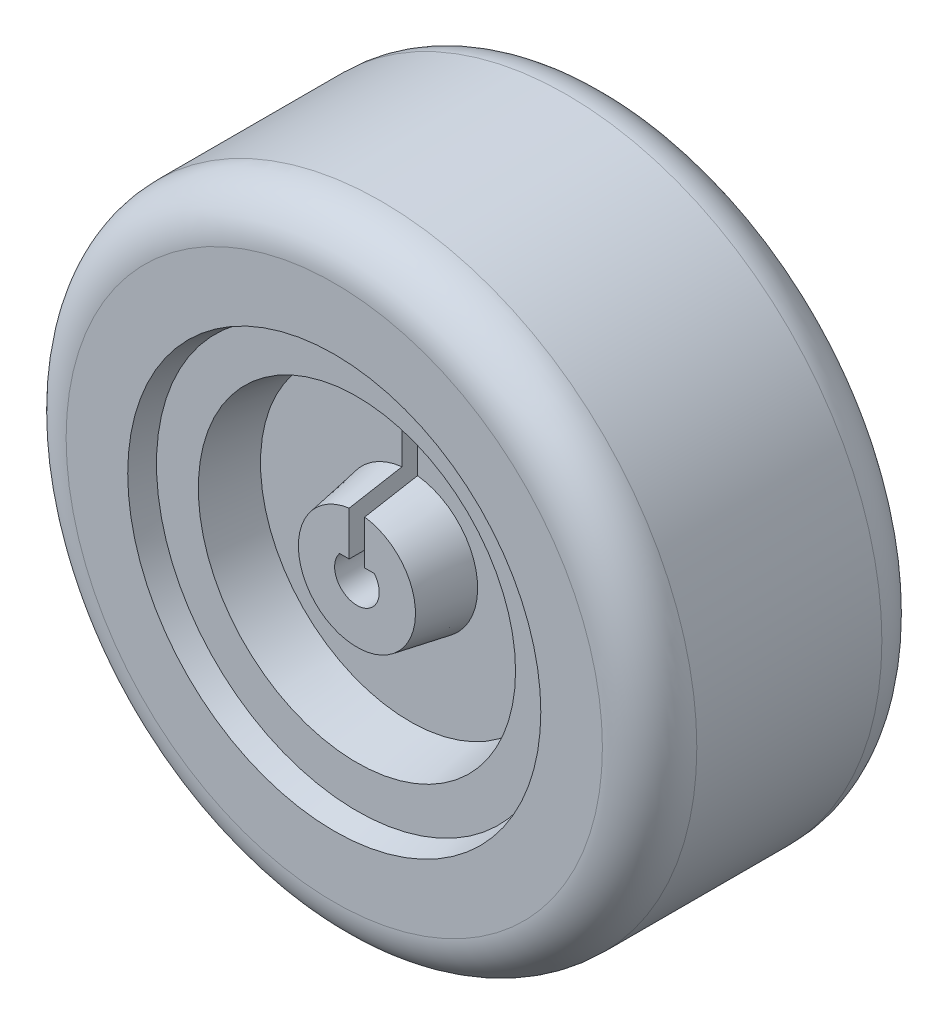
SolidWorks part; units mm, degrees
ref_plane "Front Plane" through (0, 0, 0) normal (0, 0, 1) x (1, 0, 0)
ref_plane "Top Plane" through (0, 0, 0) normal (0, 1, 0) x (1, 0, 0)
ref_plane "Right Plane" through (0, 0, 0) normal (1, 0, 0) x (0, 0, -1)
sketch "Sketch1" plane through (0, 0, 0) normal (0, 0, 1) x (1, 0, 0)
  circle A0 centre (0, 0) radius 21.209
  circle A1 centre (0, 0) radius 13.208
  dimension "D1" = 42.418
  dimension "D2" = 26.416
extrude "Boss-Extrude1" add sketch "Sketch1" along normal blind 18.796
fillet "Fillet1" radius 3.175 2 edges at (21.209, 0, 0) (21.209, 0, 18.796)
sketch "Sketch2" plane through (0, 0, 18.796) normal (0, 0, 1) x (1, 0, 0)
  circle A0 centre (0, 0) radius 13.208
  circle A1 centre (0, 0) radius 13.208 construction
extrude "Boss-Extrude2" add sketch "Sketch2" against normal offset from surface (15.748 mm away) 1.524 from offset 1.524 separate body up to face at (18.034, 0, 0) offset against normal yes
sketch "Sketch4" plane through (0, 0, 17.272) normal (0, 0, 1) x (1, 0, 0)
  circle A0 centre (0, 0) radius 3.937
  circle A2 centre (0, 0) radius 10.668
  circle A3 centre (0, 0) radius 10.668
  dimension "D2" = 7.874
  dimension "D1" = 2.54
extrude "Cut-Extrude2" cut sketch "Sketch4" against normal blind 3.556 draft 10
sketch "Sketch5" plane through (0, 0, 1.524) normal (0, 0, -1) x (-1, 0, 0)
  circle A3 centre (0, 0) radius 10.668
  circle A4 centre (0, 0) radius 10.668
  dimension "D1" = 2.54
extrude "Cut-Extrude3" cut sketch "Sketch5" against normal offset from surface (9.652 mm away) 2.54 up to face at (4.564, 0, 13.716)
sketch "Sketch6" plane through (0, 0, 11.176) normal (0, 0, -1) x (-1, 0, 0)
  circle A0 centre (0, 0) radius 4.1275
  circle A3 centre (0, 0) radius 10.668 construction
  dimension "D1" = 8.255
extrude "Boss-Extrude3" add sketch "Sketch6" along normal blind 3.81 draft 10
sketch "Sketch3" plane through (0, 0, 17.272) normal (0, 0, 1) x (1, 0, 0)
  line L0 (-1.1702, 0.9384) -> (-0.5207, 0.9384)
  line L1 (0, -1.5) -> (0, 0.9384) construction
  line L2 (0.5207, 0.9384) -> (1.1702, 0.9384)
  line L4 (-0.5207, 0.9384) -> (-0.5207, 6.7108)
  line L5 (-0.5207, 6.7108) -> (0.5207, 6.7108)
  line L6 (0.5207, 0.9384) -> (0.5207, 6.7108)
  line L7 (-0.5207, -4.834) -> (0.5207, 6.7108) construction
  line L8 (-0.5207, 6.7108) -> (0.5207, -4.834) construction
  arc A0 (-1.1702, 0.9384) -> (1.1702, 0.9384) centre (0, 0) ccw
  dimension "D1" = 3
  dimension "D2" = 2.4384
  dimension "D3" = 1.0414
extrude "Cut-Extrude1" cut sketch "Sketch3" against normal blind 20.32
chamfer "Chamfer2" distance 2.54 angle 15.06 1 edges at (13.208, 0, 18.796) first distance on face at (13.208, 0, 17.272)
chamfer "Chamfer3" distance 2.54 angle 15.06 1 edges at (13.208, 0, 0) first distance on face at (13.208, 0, 0)
sketch "Sketch8" plane through (0, 0, 1.524) normal (0, 0, -1) x (-1, 0, 0)
  line L0 (0, 0) -> (6.7819, 25.3104) construction
  line L1 (1.9316, 13.3423) -> (0.2675, 7.1318)
  line L2 (4.9984, 12.5205) -> (3.3343, 6.31)
  line L3 (0.2675, 7.1318) -> (3.3343, 6.31)
  line L4 (0, 0) -> (0, 28.6093) construction
  line L5 (8.3439, 10.589) -> (3.7975, 6.0426)
  line L6 (10.589, 8.3439) -> (6.0426, 3.7975)
  line L7 (3.7975, 6.0426) -> (6.0426, 3.7975)
  line L8 (12.5205, 4.9984) -> (6.31, 3.3343)
  line L9 (13.3423, 1.9316) -> (7.1318, 0.2675)
  line L10 (6.31, 3.3343) -> (7.1318, 0.2675)
  line L11 (13.3423, -1.9316) -> (7.1318, -0.2675)
  line L12 (12.5205, -4.9984) -> (6.31, -3.3343)
  line L13 (7.1318, -0.2675) -> (6.31, -3.3343)
  line L14 (10.589, -8.3439) -> (6.0426, -3.7975)
  line L15 (8.3439, -10.589) -> (3.7975, -6.0426)
  line L16 (6.0426, -3.7975) -> (3.7975, -6.0426)
  line L17 (4.9984, -12.5205) -> (3.3343, -6.31)
  line L18 (1.9316, -13.3423) -> (0.2675, -7.1318)
  line L19 (3.3343, -6.31) -> (0.2675, -7.1318)
  line L20 (-1.9316, -13.3423) -> (-0.2675, -7.1318)
  line L21 (-4.9984, -12.5205) -> (-3.3343, -6.31)
  line L22 (-0.2675, -7.1318) -> (-3.3343, -6.31)
  line L23 (-8.3439, -10.589) -> (-3.7975, -6.0426)
  line L24 (-10.589, -8.3439) -> (-6.0426, -3.7975)
  line L25 (-3.7975, -6.0426) -> (-6.0426, -3.7975)
  line L26 (-12.5205, -4.9984) -> (-6.31, -3.3343)
  line L27 (-13.3423, -1.9316) -> (-7.1318, -0.2675)
  line L28 (-6.31, -3.3343) -> (-7.1318, -0.2675)
  line L29 (-13.3423, 1.9316) -> (-7.1318, 0.2675)
  line L30 (-12.5205, 4.9984) -> (-6.31, 3.3343)
  line L31 (-7.1318, 0.2675) -> (-6.31, 3.3343)
  line L32 (-10.589, 8.3439) -> (-6.0426, 3.7975)
  line L33 (-8.3439, 10.589) -> (-3.7975, 6.0426)
  line L34 (-6.0426, 3.7975) -> (-3.7975, 6.0426)
  line L35 (-4.9984, 12.5205) -> (-3.3343, 6.31)
  line L36 (-1.9316, 13.3423) -> (-0.2675, 7.1318)
  line L37 (-3.3343, 6.31) -> (-0.2675, 7.1318)
  circle A0 centre (0, 0) radius 13.4814 construction
  arc A1 (4.9984, 12.5205) -> (1.9316, 13.3423) centre (0, 0) ccw
  arc A2 (10.589, 8.3439) -> (8.3439, 10.589) centre (0, 0) ccw
  arc A3 (13.3423, 1.9316) -> (12.5205, 4.9984) centre (0, 0) ccw
  arc A4 (12.5205, -4.9984) -> (13.3423, -1.9316) centre (0, 0) ccw
  arc A5 (8.3439, -10.589) -> (10.589, -8.3439) centre (0, 0) ccw
  arc A6 (1.9316, -13.3423) -> (4.9984, -12.5205) centre (0, 0) ccw
  arc A7 (-4.9984, -12.5205) -> (-1.9316, -13.3423) centre (0, 0) ccw
  arc A8 (-10.589, -8.3439) -> (-8.3439, -10.589) centre (0, 0) ccw
  arc A9 (-13.3423, -1.9316) -> (-12.5205, -4.9984) centre (0, 0) ccw
  arc A10 (-12.5205, 4.9984) -> (-13.3423, 1.9316) centre (0, 0) ccw
  arc A11 (-8.3439, 10.589) -> (-10.589, 8.3439) centre (0, 0) ccw
  arc A12 (-1.9316, 13.3423) -> (-4.9984, 12.5205) centre (0, 0) ccw
  point P56 (0, 0)
  dimension "D1" = 3.175
  dimension "D2" = 6.4296
  dimension "D3" = 15
  dimension "D4" = 12
extrude "Cut-Extrude4" cut sketch "Sketch8" against normal up to surface (5.842 mm away) up to face at (0, 0.2126, 7.366)
